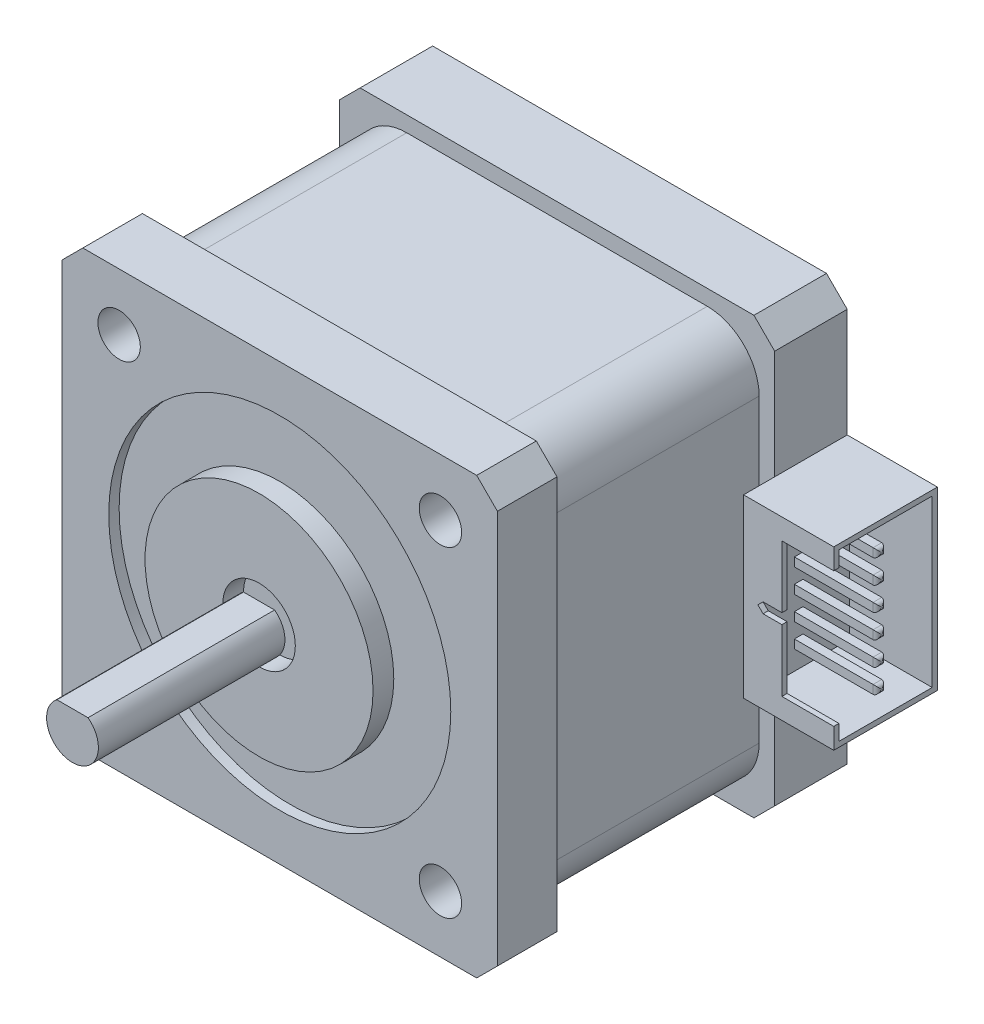
SolidWorks part; units mm, degrees
ref_plane "Alzado" through (0, 0, 0) normal (0, 0, 1) x (1, 0, 0)
ref_plane "Planta" through (0, 0, 0) normal (0, 1, 0) x (1, 0, 0)
ref_plane "Vista lateral" through (0, 0, 0) normal (1, 0, 0) x (0, 0, -1)
sketch "Croquis3" plane through (0, 0, 0) normal (0, 0, 1) x (1, 0, 0)
  line L0 (-1.5, 2) -> (1.5, 2)
  arc A0 (-1.5, 2) -> (1.5, 2) centre (0, 0) ccw
  dimension "D1" = 5
  dimension "D2" = 2
extrude "Saliente-Extruir1" add sketch "Croquis3" along normal blind 53.75
sketch "Croquis5" plane through (0, 0, 0) normal (0, 0, 1) x (1, 0, 0)
  line L1 (-21, 21) -> (21, 21)
  line L2 (-21, 21) -> (-21, -21)
  line L3 (-21, -21) -> (21, -21)
  line L4 (21, 21) -> (21, -21)
  line L5 (29.7, -8.5) -> (21, -8.5)
  line L6 (29.7, -8.5) -> (29.7, 8.5)
  line L7 (29.7, 8.5) -> (21, 8.5)
  line L8 (21, -8.5) -> (21, 8.5)
  dimension "D1" = 42
  dimension "D2" = 42
  dimension "D3" = 17
  dimension "D4" = 8.7
  dimension "D5" = 12.5
extrude "Saliente-Extruir2" add sketch "Croquis5" along normal blind 7 contours L4 L1 L2 L3 region at (0, 0, 0)
extrude "Saliente-Extruir3" add sketch "Croquis5<3>" along normal blind 10 contours L6 L7 L4 L5 region at (25.35, 0, 0)
sketch "Croquis5<3>" plane through (0, 0, 0) normal (0, 0, 1) x (1, 0, 0) same geometry as "Croquis5"
sketch "Croquis6" plane through (0, 0, 7) normal (0, 0, 1) x (1, 0, 0)
  line L1 (-19.5, 19.5) -> (19.5, 19.5)
  line L2 (-19.5, 19.5) -> (-19.5, -19.5)
  line L3 (-19.5, -19.5) -> (19.5, -19.5)
  line L4 (19.5, 19.5) -> (19.5, -19.5)
  point P8 (0, -19.5)
  point P9 (-19.5, 0)
  dimension "D1" = 39
extrude "Saliente-Extruir4" add sketch "Croquis6" along normal blind 21
sketch "Croquis7" plane through (0, 0, 28) normal (0, 0, 1) x (1, 0, 0)
  line L1 (-21, 21) -> (21, 21)
  line L2 (-21, 21) -> (-21, -21)
  line L3 (-21, -21) -> (21, -21)
  line L4 (21, 21) -> (21, -21)
extrude "Saliente-Extruir5" add sketch "Croquis7" along normal blind 5.75
sketch "Croquis8" plane through (0, 0, 33.75) normal (0, 0, 1) x (1, 0, 0)
  circle A0 centre (0, 0) radius 11
  dimension "D1" = 22
extrude "Saliente-Extruir6" add sketch "Croquis8" along normal blind 2
sketch "Croquis9" plane through (0, 0, 33.75) normal (0, 0, 1) x (1, 0, 0)
  circle A0 centre (0, 0) radius 16.5
  dimension "D1" = 33
extrude "Cortar-Extruir3" cut sketch "Croquis9" against normal blind 1
sketch "Croquis10" plane through (0, 0, 35.75) normal (0, 0, 1) x (1, 0, 0)
  circle A0 centre (0, 0) radius 3.5
  dimension "D1" = 7
extrude "Cortar-Extruir4" cut sketch "Croquis10" against normal blind 3
chamfer "Chaflán1" distance 2 angle 45 8 edges at (21, -21, 3.5) (21, -21, 30.875) (21, 21, 30.875) (21, 21, 3.5) (-21, 21, 30.875) (-21, 21, 3.5) (-21, -21, 3.5) (-21, -21, 30.875)
fillet "Redondeo1" radius 5 4 edges at (19.5, -19.5, 17.5) (-19.5, -19.5, 17.5) (-19.5, 19.5, 17.5) (19.5, 19.5, 17.5)
sketch "Croquis11" plane through (0, 0, 33.75) normal (0, 0, 1) x (1, 0, 0)
  line L0 (19, 21) -> (-19, 21) construction
  line L1 (-21, 19) -> (-21, -19) construction
  circle A0 centre (-15.5, 15.5) radius 2.0458
  circle A1 centre (15.5, 15.5) radius 2.0458
  circle A2 centre (15.5, -15.5) radius 2.0458
  circle A3 centre (-15.5, -15.5) radius 2.0458
  dimension "D1" = 5.5
  dimension "D2" = 5.5
  dimension "D3" = 2
  dimension "D4" = 2
sketch "Croquis12" plane through (0, 0, 0) normal (0, 0, 1) x (1, 0, 0)
  circle A0 centre (-15.5, 15.5) radius 2.0458
  circle A1 centre (15.5, 15.5) radius 2.0458
  circle A2 centre (15.5, -15.5) radius 2.0458
  circle A3 centre (-15.5, -15.5) radius 2.0458
  dimension "D3" = 2
  dimension "D4" = 2
extrude "Cortar-Extruir5" cut sketch "Croquis11" against normal blind 5
extrude "Cortar-Extruir6" cut sketch "Croquis12" along normal blind 5
sketch "Croquis13" plane through (29.7, 0, 0) normal (1, 0, 0) x (0, 0, -1)
  line L0 (-9.5, 8) -> (-9.5, -8)
  line L5 (-9.5, -8) -> (-0.5, -8)
  line L6 (-0.5, 8) -> (-0.5, -8)
  line L7 (-9.5, 8) -> (-0.5, 8)
extrude "Cortar-Extruir7" cut sketch "Croquis13" against normal blind 8
sketch "Croquis15" plane through (0, 0, 10) normal (0, 0, 1) x (1, 0, 0)
  line L0 (29.7, -6.5) -> (29.7, 6.5)
  line L1 (29.7, -8.5) -> (29.7, 8.5) construction
  line L2 (29.7, -8.5) -> (21, -8.5) construction
  line L3 (29.7, -6.5) -> (24.7, -6.5)
  line L4 (24.7, -6.5) -> (24.7, -0.5)
  line L5 (24.7, -0.5) -> (22.3815, -0.5)
  line L6 (22.3815, -0.5) -> (22.3815, 0)
  line L7 (22.3815, 0) -> (22.3815, 0.5)
  line L8 (22.3815, 0.5) -> (24.7, 0.5)
  line L9 (24.7, 0.5) -> (24.7, 6.5)
  line L10 (24.7, 6.5) -> (29.7, 6.5)
  dimension "D1" = 2
  dimension "D2" = 2
  dimension "D3" = 6
  dimension "D4" = 5
extrude "Cortar-Extruir9" cut sketch "Croquis15" against normal blind 0.5
chamfer "Chaflán2" distance 0.5 angle 45 2 edges at (22.3815, -0.5, 9.75) (22.3815, 0.5, 9.75)
sketch "Croquis16" plane through (21.7, 0, 0) normal (1, 0, 0) x (0, 0, -1)
  line L0 (-5.3837, 8) -> (-5.3837, 5.7143) construction
  line L1 (-0.5, 8) -> (-9.5, 8) construction
  line L2 (-5.3837, 5.7143) -> (-5.3837, 3.4286) construction
  line L3 (-5.3837, 3.4286) -> (-5.3837, 1.1429) construction
  line L4 (-5.3837, 1.1429) -> (-5.3837, -1.1429) construction
  line L5 (-5.3837, -1.1429) -> (-5.3837, -3.4286) construction
  line L6 (-5.3837, -3.4286) -> (-5.3837, -5.7143) construction
  line L7 (-5.3837, -5.7143) -> (-5.3837, -8) construction
  line L8 (-9.5, -8) -> (-0.5, -8) construction
  line L9 (-5.3837, 5.7143) -> (-5.3837, 6.1308) construction
  line L10 (-5.8003, 6.1308) -> (-4.9672, 6.1308)
  line L11 (-5.8003, 6.1308) -> (-5.8003, 5.2978)
  line L12 (-5.8003, 5.2978) -> (-4.9672, 5.2978)
  line L13 (-4.9672, 6.1308) -> (-4.9672, 5.2978)
  line L14 (-5.3837, 5.7143) -> (-5.8003, 5.7143) construction
  line L19 (-5.3837, -5.7143) -> (-5.3837, -5.2978) construction
  line L20 (-5.8003, -5.2978) -> (-4.9672, -5.2978)
  line L21 (-5.8003, -5.2978) -> (-5.8003, -6.1308)
  line L22 (-5.8003, -6.1308) -> (-4.9672, -6.1308)
  line L23 (-4.9672, -5.2978) -> (-4.9672, -6.1308)
  line L24 (-5.3837, -5.7143) -> (-5.8003, -5.7143) construction
  line L25 (-5.3837, -3.4286) -> (-5.3837, -3.0121) construction
  line L26 (-5.8003, -3.0121) -> (-4.9672, -3.0121)
  line L27 (-5.8003, -3.0121) -> (-5.8003, -3.8451)
  line L28 (-5.8003, -3.8451) -> (-4.9672, -3.8451)
  line L29 (-4.9672, -3.0121) -> (-4.9672, -3.8451)
  line L30 (-5.3837, -3.4286) -> (-5.8003, -3.4286) construction
  line L31 (-5.3837, -1.1429) -> (-5.3837, -0.7263) construction
  line L36 (-5.8003, -0.7263) -> (-4.9672, -0.7263)
  line L37 (-5.8003, -0.7263) -> (-5.8003, -1.5594)
  line L38 (-5.8003, -1.5594) -> (-4.9672, -1.5594)
  line L39 (-4.9672, -0.7263) -> (-4.9672, -1.5594)
  line L40 (-5.3837, -1.1429) -> (-5.8003, -1.1429) construction
  line L41 (-5.3837, 1.1429) -> (-5.3837, 1.5594) construction
  line L46 (-5.8003, 1.5594) -> (-4.9672, 1.5594)
  line L47 (-5.8003, 1.5594) -> (-5.8003, 0.7263)
  line L48 (-5.8003, 0.7263) -> (-4.9672, 0.7263)
  line L49 (-4.9672, 1.5594) -> (-4.9672, 0.7263)
  line L50 (-5.3837, 1.1429) -> (-5.8003, 1.1429) construction
  line L51 (-5.3837, 3.4286) -> (-5.3837, 3.8451) construction
  line L52 (-5.8003, 3.8451) -> (-4.9672, 3.8451)
  line L53 (-5.8003, 3.8451) -> (-5.8003, 3.0121)
  line L54 (-5.8003, 3.0121) -> (-4.9672, 3.0121)
  line L55 (-4.9672, 3.8451) -> (-4.9672, 3.0121)
  line L56 (-5.3837, 3.4286) -> (-5.8003, 3.4286) construction
  point P16 (-5.3837, 5.7143)
  point P25 (-5.3837, -5.7143)
  point P33 (-5.3837, -3.4286)
  point P41 (-5.3837, -1.1429)
  point P49 (-5.3837, 1.1429)
  point P57 (-5.3837, 3.4286)
extrude "Saliente-Extruir7" add sketch "Croquis16" along normal blind 8
fillet "Redondeo19" radius 0.4 24 edges at (29.7, 6.1308, 5.3837) (29.7, 5.7143, 4.9672) (29.7, 5.2978, 5.3837) (29.7, 5.7143, 5.8003) (29.7, 3.8451, 5.3837) (29.7, 3.4286, 4.9672) (29.7, 3.0121, 5.3837) (29.7, 3.4286, 5.8003) (29.7, 1.5594, 5.3837) (29.7, 1.1429, 4.9672) (29.7, 0.7263, 5.3837) (29.7, 1.1429, 5.8003) (29.7, -0.7263, 5.3837) (29.7, -1.1429, 4.9672) (29.7, -1.5594, 5.3837) (29.7, -1.1429, 5.8003) (29.7, -3.0121, 5.3837) (29.7, -3.4286, 4.9672) (29.7, -3.8451, 5.3837) (29.7, -3.4286, 5.8003) (29.7, -5.2978, 5.3837) (29.7, -5.7143, 4.9672) (29.7, -6.1308, 5.3837) (29.7, -5.7143, 5.8003)
